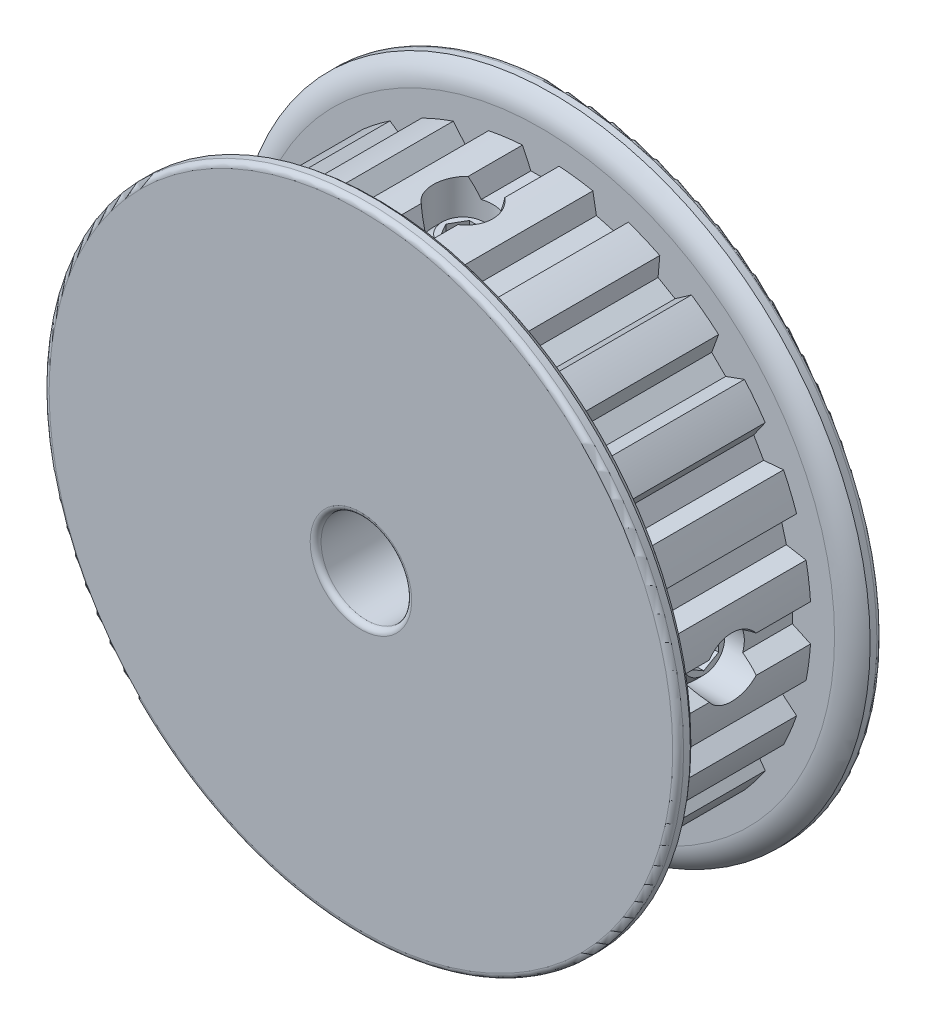
SolidWorks part; units mm, degrees
note: '?' marks a value the reader was unsure of.
ref_plane "Front Plane" through (0, 0, 0) normal (0, 0, 1) x (1, 0, 0)
ref_plane "Top Plane" through (0, 0, 0) normal (0, 1, 0) x (1, 0, 0)
ref_plane "Right Plane" through (0, 0, 0) normal (1, 0, 0) x (0, 0, -1)
sketch "Sketch1" plane through (0, 0, 0) normal (0, 0, 1) x (1, 0, 0)
  line L0 (-1.2827, 18.8976) -> (-0.6905, 17.6276)
  line L1 (-0.6905, 17.6276) -> (0.6905, 17.6276)
  line L2 (0.6905, 17.6276) -> (1.2827, 18.8976)
  line L3 (-1.2827, 18.8976) -> (1.2827, 18.8976)
  line L4 (0, 0) -> (0, 17.6276) construction
  line L5 (0, 17.6276) -> (0, 19.9136) construction
  circle A0 centre (0, 0) radius 19.4056 construction
  circle A1 centre (0, 0) radius 22.225 construction
  circle A2 centre (0, 0) radius 18.9411 construction
  point P6 (0, 18.8976)
  point P11 (0, 19.4056)
  point P13 (0, 22.225)
  point P14 (0, 18.9411)
  dimension "D1" = 1.016
  dimension "PD" = 38.8112
  dimension "D2" = 0.508
  dimension "OD" = 44.45
  dimension "b" = 50
  dimension "bt" = 2.5654
  dimension "ht" = 1.27
  dimension "hs" = 2.286
sketch "Sketch2" plane through (0, 0, 0) normal (1, 0, 0) x (0, 0, -1)
  line L0 (-7.1501, 3.175) -> (7.1501, 3.175)
  line L3 (-7.1501, 3.175) -> (-7.1501, 22.225)
  line L4 (-7.1501, 22.225) -> (-5.4483, 22.225) construction
  line L5 (-5.4483, 22.225) -> (-5.4483, 18.9411) construction
  line L6 (-5.4483, 18.9411) -> (5.4483, 18.9411)
  line L7 (5.4483, 18.9411) -> (5.4483, 22.225) construction
  line L8 (5.4483, 22.225) -> (7.1501, 22.225) construction
  line L9 (7.1501, 22.225) -> (7.1501, 3.175)
  line L10 (-7.1501, 0) -> (7.1501, 0) construction
  line L13 (-7.1501, 22.225) -> (-6.2992, 22.225)
  line L14 (-5.4483, 20.583) -> (-5.4483, 18.9411)
  line L15 (5.4483, 18.9411) -> (5.4483, 20.583)
  line L16 (6.2992, 22.225) -> (7.1501, 22.225)
  arc A0 (-5.4483, 20.583) -> (-6.2992, 22.225) centre (-7.458, 20.583) ccw
  arc A1 (5.4483, 20.583) -> (6.2992, 22.225) centre (7.458, 20.583) cw
  point P12 (-5.4483, 20.583)
  point P14 (-6.2992, 22.225)
  point P20 (5.4483, 20.583)
  point P21 (6.2992, 22.225)
  point P25 (5.4483, 0)
  point P26 (-5.4483, 0)
  dimension "OA" = 14.3002
  dimension "Bore" = 6.35
  dimension "Outside Width" = 14.3002
  dimension "Inside Width" = 10.8966
revolve "Revolve1" add sketch "Sketch2" angle 360 mid plane about L10
sketch "Sketch3" plane through (0, 0, 0) normal (0, 0, 1) x (1, 0, 0)
  line L0 (-0.6905, 17.6276) -> (0.6905, 17.6276) construction
  line L1 (0.6905, 17.6276) -> (1.2827, 18.8976) construction
  line L2 (-1.2827, 18.8976) -> (-0.6905, 17.6276) construction
  line L3 (-0.6905, 17.6276) -> (0.6905, 17.6276)
  line L4 (0.6905, 17.6276) -> (1.2827, 18.8976)
  line L5 (-1.2827, 18.8976) -> (-0.6905, 17.6276)
  circle A0 centre (0, 0) radius 18.9411 construction
  arc A1 (1.2827, 18.8976) -> (-1.2827, 18.8976) centre (0, 0) ccw
extrude "Cut-Extrude1" cut sketch "Sketch3" against normal up to vertex (5.4483 mm away) from vertex at 5.4483 starting at point (0, 18.9411, 5.4483)
pattern_circular "CirPattern1" count 24 over 360 about axis through (0, 0, 0) along (0, 0, 1) of "Cut-Extrude1"
fillet "Fillet1" radius 0.381 4 edges at (3.175, 0, -7.1501) (22.225, 0, -7.1501) (22.225, 0, 7.1501) (3.175, 0, 7.1501)
sketch "Sketch5" plane through (0, 0, 0) normal (0, 1, 0) x (1, 0, 0)
  line L1 (1.2827, 0) -> (-1.2827, 0) construction
  line L2 (1.2827, 5.4483) -> (1.2827, -5.4483) construction
  line L3 (-1.2827, 5.4483) -> (-1.2827, -5.4483) construction
  circle A0 centre (0, 0) radius 2.0828
extrude "Cut-Extrude2" cut sketch "Sketch5" along normal through all
sketch "Sketch6" plane through (0, 0, 0) normal (1, 0, 0) x (0, 0, -1)
  line L0 (0, 16.8656) -> (0, 3.937)
  line L1 (6.7691, 3.175) -> (-6.7691, 3.175) construction
  line L3 (2.0828, 17.6276) -> (-2.0828, 17.6276) construction
  line L4 (-1.965, 17.6276) -> (-2.0828, 17.6276) construction
  line L5 (2.0828, 17.6276) -> (1.965, 17.6276) construction
  line L6 (0, 16.8656) -> (-1.458, 16.8656)
  line L7 (-1.458, 16.8656) -> (-2.0828, 16.2408)
  line L8 (-2.0828, 16.2408) -> (-2.0828, 4.5618)
  line L9 (-2.0828, 4.5618) -> (-1.458, 3.937)
  line L10 (-1.458, 3.937) -> (0, 3.937)
  point P12 (0, 3.175)
  point P19 (0, 17.6276)
  dimension "D1" = 0.762
  dimension "D2" = 0.762
  dimension "D3" = 135
  dimension "D4" = 0.6248
revolve "Revolve2" add sketch "Sketch6" angle 360 about L0
sketch "Sketch7" plane through (0, 16.8656, 0) normal (0, 1, 0) x (1, 0, 0)
  line L1 (1.2025, 0) -> (0.6013, 1.0414)
  line L2 (0.6013, 1.0414) -> (-0.6013, 1.0414)
  line L3 (-0.6013, 1.0414) -> (-1.2025, 0)
  line L4 (-1.2025, 0) -> (-0.6013, -1.0414)
  line L5 (-0.6013, -1.0414) -> (0.6013, -1.0414)
  line L6 (0.6013, -1.0414) -> (1.2025, 0)
  circle A0 centre (0, 0) radius 1.0414 construction
  dimension "D1" = 2.0828
extrude "Cut-Extrude3" cut sketch "Sketch7" against normal blind 1.0414
pattern_circular "CirPattern2" count 2 over 270 about axis through (0, 0, 0) along (0, 0, 1) of "Cut-Extrude2", "Revolve2", "Cut-Extrude3"
ref_axis "Center Axis 1" through (0, 0, -6.7691) along (0, 0, 1)?
ref_plane "Contact Plane 1" through (0, 0, 7.1501) normal (0, 0, 1) x (1, 0, 0)
ref_plane "Contact Plane 2" through (0, 0, -7.1501) normal (0, 0, -1) x (-1, 0, 0)
equation "\"D4@Sketch6\" = \"Set Screw Dia@Sketch5\" * .15"
equation "\"D1@Sketch7\" = \"Set Screw Dia@Sketch5\" / 2"
equation "\"D1@Cut-Extrude3\" = \"Set Screw Dia@Sketch5\" / 4"
